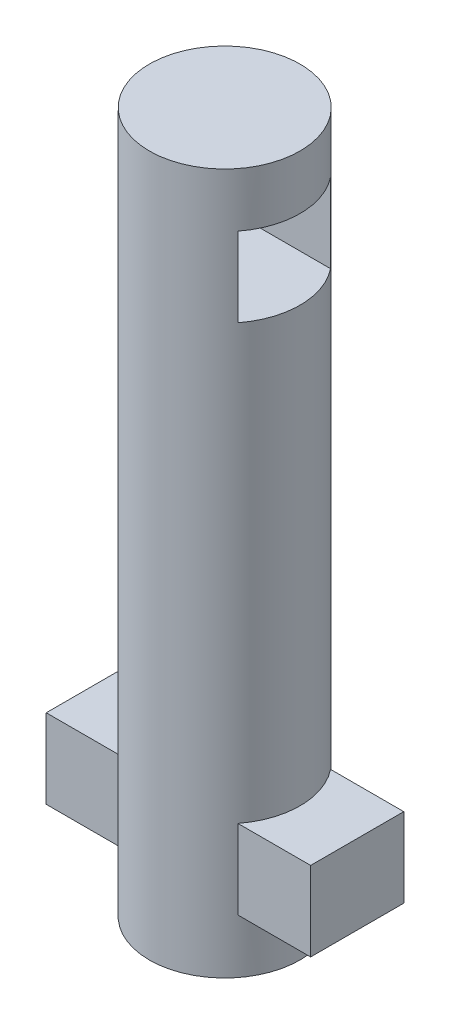
SolidWorks part; units mm, degrees
ref_plane "前视基准面" through (0, 0, 0) normal (0, 0, 1) x (1, 0, 0)
ref_plane "上视基准面" through (0, 0, 0) normal (0, 1, 0) x (1, 0, 0)
ref_plane "右视基准面" through (0, 0, 0) normal (1, 0, 0) x (0, 0, -1)
sketch "草图1" plane through (0, 0, 0) normal (0, 1, 0) x (1, 0, 0)
  circle A0 centre (0, 0) radius 5.7
extrude "凸台-拉伸1" add sketch "草图1" along normal blind 53
sketch "草图2" plane through (0, 0, 0) normal (1, 0, 0) x (0, 0, -1)
  line L0 (0, 53) -> (0, 0) construction
  line L1 (5.7, 53) -> (-5.7, 53) construction
  line L2 (0, 0) -> (0, 26.5) construction
  line L3 (0, 26.5) -> (0, 10.1) construction
  line L4 (0, 10.1) -> (0, 42.9) construction
  line L5 (0, 42.9) -> (0, 48.9) construction
  line L6 (0, 48.9) -> (-3.5, 48.9) construction
  line L7 (-3.5, 48.9) -> (-3.5, 42.9) construction
  line L8 (0, 10.1) -> (0, 4.1) construction
  line L9 (-3.5, 4.6441) -> (-3.5, 10.1) construction
  line L11 (-3.5, 42.9) -> (3.5455, 42.9)
  line L12 (-3.5, 42.9) -> (-3.5, 48.9)
  line L13 (-3.5, 48.9) -> (3.5455, 48.9)
  line L14 (3.5455, 42.9) -> (3.5455, 48.9)
  line L15 (-3.5, 10.1) -> (3.5455, 10.1)
  line L16 (-3.5, 10.1) -> (-3.5, 4.1)
  line L17 (-3.5, 4.1) -> (3.5455, 4.1)
  line L18 (3.5455, 10.1) -> (3.5455, 4.1)
  dimension "D1" = 16.4
  dimension "D2" = 16.4
  dimension "D3" = 3.5
  dimension "D4" = 6
  dimension "D5" = 6
extrude "切除-拉伸1" cut sketch "草图2" along normal through all both and the other way through all contours L11 L14 L13 L12
extrude "凸台-拉伸2" add sketch "草图2<4>" along normal blind 10 and the other way blind 10 contours L16 L15 L18 L17
sketch "草图2<4>" plane through (0, 0, 0) normal (1, 0, 0) x (0, 0, -1) same geometry as "草图2"
